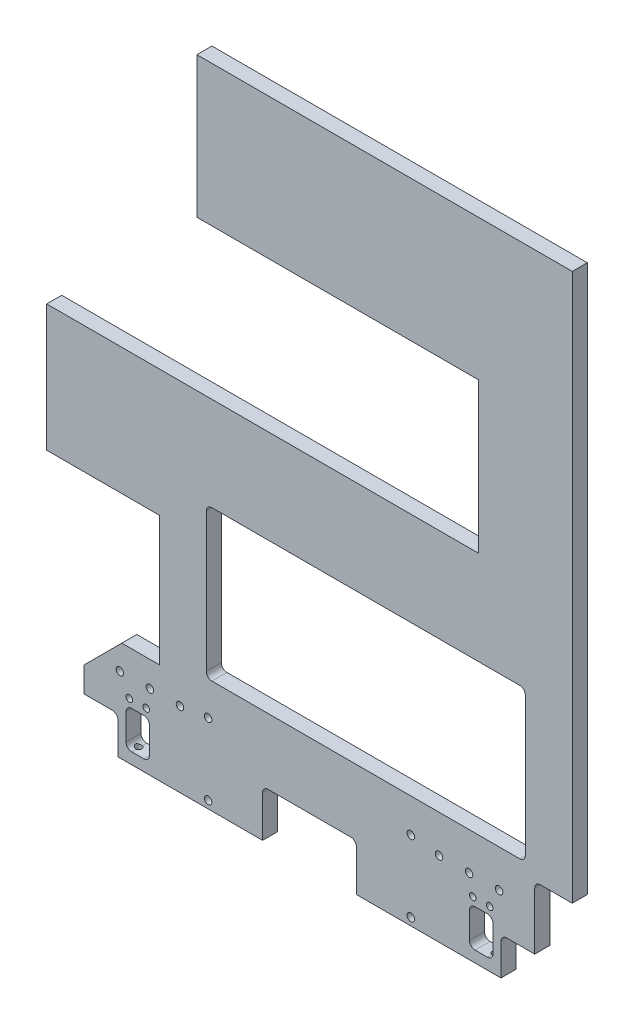
SolidWorks part; units mm, degrees
ref_plane "Front" through (0, 0, 0) normal (0, 0, 1) x (1, 0, 0)
ref_plane "Top" through (0, 0, 0) normal (0, 1, 0) x (1, 0, 0)
ref_plane "Right" through (0, 0, 0) normal (1, 0, 0) x (0, 0, -1)
sketch "Esquisse1" plane through (0, 0, 0) normal (0, 0, 1) x (1, 0, 0)
  line L1 (0, 0) -> (280, 0)
  line L2 (0, 0) -> (0, 45)
  line L3 (0, 45) -> (280, 45)
  line L4 (280, 0) -> (280, 45)
  dimension "D1" = 280
  dimension "D2" = 45
extrude "Boss.-Extru.1" add sketch "Esquisse1" along normal blind 8
sketch "Esquisse3" plane through (0, 0, 8) normal (0, 0, 1) x (1, 0, 0)
  line L0 (140, 0) -> (140, 32.6648) construction
  line L1 (0, 0) -> (38, 0)
  line L2 (0, 0) -> (0, 20)
  line L3 (0, 20) -> (38, 20)
  line L4 (38, 0) -> (38, 20)
  line L5 (0, 0) -> (280, 0) construction
  line L6 (242, 0) -> (242, 20)
  line L7 (280, 20) -> (242, 20)
  line L8 (280, 0) -> (280, 20)
  line L9 (280, 0) -> (242, 0)
  dimension "D1" = 20
  dimension "D2" = 38
extrude "Enlèv. mat.-Extru.2" cut sketch "Esquisse3" against normal through all
sketch "Esquisse2" plane through (0, 0, 8) normal (0, 0, 1) x (1, 0, 0)
  line L0 (140, 0) -> (140, 45) construction
  line L1 (38, 0) -> (242, 0) construction
  line L2 (280, 45) -> (0, 45) construction
  line L3 (86, 4) -> (86, 42) construction
  line L4 (194, 4) -> (194, 42) construction
  circle A0 centre (86, 4) radius 2
  circle A1 centre (86, 42) radius 2
  circle A2 centre (194, 42) radius 2
  circle A3 centre (194, 4) radius 2
  dimension "D1" = 4
  dimension "D3" = 4
  dimension "D2" = 54
  dimension "D4" = 38
extrude "Enlèv. mat.-Extru.1" cut sketch "Esquisse2" against normal through all
sketch "Esquisse4" plane through (0, 0, 8) normal (0, 0, 1) x (1, 0, 0)
  line L0 (39, 40) -> (71, 40) construction
  line L1 (140, 0) -> (140, 45) construction
  line L2 (38, 0) -> (242, 0) construction
  line L3 (280, 45) -> (0, 45) construction
  line L4 (241, 40) -> (209, 40) construction
  line L5 (236, 30) -> (227, 30) construction
  line L6 (44, 30) -> (53, 30) construction
  line L7 (231.5, 26) -> (231.5, 30) construction
  line L8 (225.25, 26) -> (237.75, 26)
  line L9 (225.25, 26) -> (225.25, 6)
  line L10 (225.25, 6) -> (237.75, 6)
  line L11 (237.75, 26) -> (237.75, 6)
  line L12 (42.25, 26) -> (42.25, 6)
  line L13 (54.75, 6) -> (42.25, 6)
  line L14 (54.75, 26) -> (54.75, 6)
  line L15 (54.75, 26) -> (42.25, 26)
  circle A0 centre (71, 40) radius 2
  circle A1 centre (39, 40) radius 2
  circle A2 centre (55, 40) radius 2
  circle A3 centre (225, 40) radius 2
  circle A4 centre (241, 40) radius 2
  circle A5 centre (209, 40) radius 2
  circle A6 centre (236, 30) radius 1.75
  circle A7 centre (227, 30) radius 1.75
  circle A9 centre (53, 30) radius 1.75
  circle A10 centre (44, 30) radius 1.75
  circle A11 centre (194, 4) radius 2 construction
  dimension "D1" = 4
  dimension "D2" = 16
  dimension "D5" = 3.5
  dimension "D7" = 33
  dimension "D3" = 40
  dimension "D4" = 170
  dimension "D6" = 9
  dimension "D8" = 30
  dimension "D9" = 20
  dimension "D10" = 12.5
  dimension "D11" = 4
extrude "Enlèv. mat.-Extru.3" cut sketch "Esquisse4" against normal through all
sketch "Esquisse5" plane through (0, 0, 0) normal (0, -1, 0) x (-1, 0, 0)
  line L0 (-38, -4) -> (-242, -4) construction
  line L1 (-38, 0) -> (-38, -8) construction
  line L2 (-242, 0) -> (-242, -8) construction
  line L3 (-140, -4) -> (-140, -7.2082) construction
  circle A0 centre (-180, -4) radius 1.65
  circle A1 centre (-235, -4) radius 1.65
  circle A2 centre (-45, -4) radius 1.65
  circle A3 centre (-100, -4) radius 1.65
  dimension "D1" = 3.3
  dimension "D2" = 95
  dimension "D3" = 80
extrude "Enlèv. mat.-Extru.4" cut sketch "Esquisse5" against normal blind 10
sketch "Esquisse6" plane through (0, 0, 0) normal (0, 0, -1) x (-1, 0, 0)
  line L0 (-38, 0) -> (-242, 0) construction
  line L1 (-165, 25) -> (-115, 25)
  line L2 (-165, 25) -> (-165, 0)
  line L3 (-165, 0) -> (-115, 0)
  line L4 (-115, 25) -> (-115, 0)
  line L5 (-140, 25) -> (-140, 45) construction
  line L6 (-280, 45) -> (0, 45) construction
  dimension "D1" = 50
  dimension "D2" = 25
extrude "Enlèv. mat.-Extru.5" cut sketch "Esquisse6" against normal through all
sketch "Esquisse7" plane through (0, 0, 8) normal (0, 0, 1) x (1, 0, 0)
  line L0 (0, 45) -> (280, 45)
  line L1 (280, 45) -> (280, 345)
  line L2 (280, 345) -> (0, 345)
  line L3 (0, 345) -> (0, 45)
  dimension "D1" = 300
extrude "Boss.-Extru.2" add sketch "Esquisse7" against normal up to vertex (8 mm away) up to point (0, 45, 0)
sketch "Esquisse8" plane through (0, 0, 8) normal (0, 0, 1) x (1, 0, 0)
  line L1 (85, 140) -> (255, 140)
  line L2 (85, 140) -> (85, 60)
  line L3 (85, 60) -> (255, 60)
  line L4 (255, 140) -> (255, 60)
  line L5 (280, 20) -> (280, 345) construction
  line L6 (38, 0) -> (115, 0) construction
  dimension "D1" = 80
  dimension "D2" = 170
  dimension "D3" = 25
  dimension "D4" = 60
extrude "Enlèv. mat.-Extru.6" cut sketch "Esquisse8" against normal through all
sketch "Esquisse9" plane through (0, 0, 8) normal (0, 0, 1) x (1, 0, 0)
  line L0 (0, 345) -> (0, 20) construction
  line L1 (0, 53.5) -> (60, 53.5)
  line L2 (0, 53.5) -> (0, 122.5)
  line L3 (0, 122.5) -> (60, 122.5)
  line L4 (60, 53.5) -> (60, 122.5)
  line L5 (38, 0) -> (115, 0) construction
  dimension "D1" = 60
  dimension "D2" = 69
  dimension "D3" = 53.5
extrude "Enlèv. mat.-Extru.7" cut sketch "Esquisse9" against normal through all
sketch "Esquisse10" plane through (0, 0, 8) normal (0, 0, 1) x (1, 0, 0)
  line L0 (0, 53.5) -> (60, 53.5) construction
  line L1 (0, 20) -> (20, 20)
  line L2 (0, 20) -> (0, 53.5)
  line L3 (0, 53.5) -> (20, 53.5)
  line L4 (20, 20) -> (20, 53.5)
  line L5 (140, 345) -> (140, 248.098) construction
  line L6 (280, 345) -> (0, 345) construction
  line L7 (260, 20) -> (260, 53.5)
  line L8 (280, 53.5) -> (260, 53.5)
  line L9 (280, 20) -> (280, 53.5)
  line L10 (280, 20) -> (260, 20)
  dimension "D1" = 20
extrude "Enlèv. mat.-Extru.8" cut sketch "Esquisse10" against normal through all
chamfer "Chanfrein1" distance 20 angle 45 1 edges at (20, 53.5, 4)
fillet "Congé1" radius 3 17 edges at (242, 20, 4) (237.75, 6, 4) (237.75, 26, 4) (225.25, 26, 4) (225.25, 6, 4) (54.75, 26, 4) (54.75, 6, 4) (42.25, 6, 4) (42.25, 26, 4) (38, 20, 4) (115, 25, 4) (165, 25, 4) (260, 53.5, 4) (85, 140, 4) (255, 140, 4) (255, 60, 4) (85, 60, 4)
sketch "Esquisse11" plane through (0, 0, 8) normal (0, 0, 1) x (1, 0, 0)
  line L1 (0, 270) -> (230, 270)
  line L2 (0, 270) -> (0, 190)
  line L3 (0, 190) -> (230, 190)
  line L4 (230, 270) -> (230, 190)
  line L6 (38, 0) -> (115, 0) construction
  line L7 (0, 345) -> (0, 122.5) construction
  point P4 (182.2718, 204.3232)
  point P5 (0, 203.75)
  point P8 (0, 0)
  point P9 (0, 200)
  dimension "D1" = 80
  dimension "D2" = 190
  dimension "D3" = 230
extrude "Enlèv. mat.-Extru.9" cut sketch "Esquisse11" against normal through all
sketch "Esquisse12" plane through (0, 0, 8) normal (0, 0, 1) x (1, 0, 0)
  line L0 (280, 345) -> (0, 345) construction
  line L1 (0, 270) -> (80, 270)
  line L2 (0, 270) -> (0, 345)
  line L3 (0, 345) -> (80, 345)
  line L4 (80, 270) -> (80, 345)
  dimension "D1" = 80
extrude "Enlèv. mat.-Extru.10" cut sketch "Esquisse12" against normal through all
